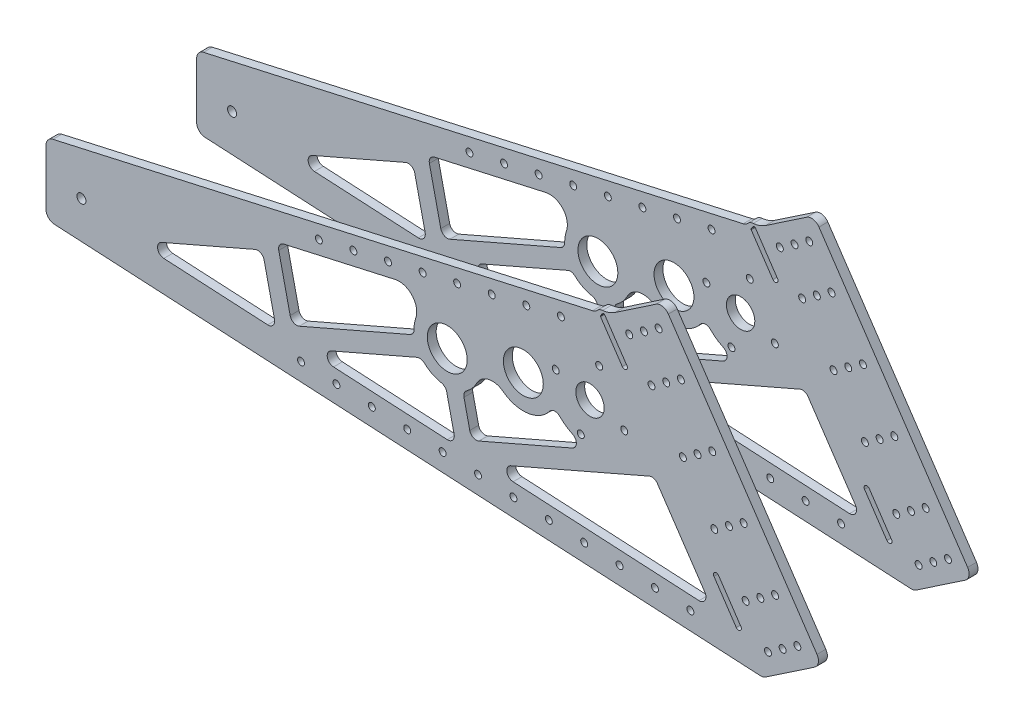
SolidWorks part; units mm, degrees
other "Markup1"
sketch "Sketch2"
sketch "Sketch9" plane through (0, 0, 0) normal (0, 0, 1) x (1, 0, 0)
sketch "Sketch12" plane through (116.0373, 167.646, 63.5) normal (0, 0, 1) x (1, 0, 0)
sketch "Sketch13" plane through (116.0373, 167.646, 63.5) normal (0, 0, 1) x (1, 0, 0)
sketch "Sketch14" plane through (116.0373, 167.646, 63.5) normal (0, 0, 1) x (1, 0, 0)
sketch "Sketch16" plane through (116.0373, 167.646, 63.5) normal (0, 0, 1) x (1, 0, 0)
sketch "Sketch17" plane through (116.0373, 167.8557, 63.5) normal (0, 0, 1) x (1, 0, 0)
sketch "Sketch18" plane through (116.0373, 167.7906, 57.15) normal (0, 0, 1) x (1, 0, 0)
sketch "Sketch19" plane through (84.5137, 127.089, 57.15) normal (0, 0, 1) x (1, 0, 0)
sketch "Sketch21" plane through (128.7373, 167.7931, 57.15) normal (0, 0, 1) x (1, 0, 0)
material "6061-T6 (SS)"
ref_plane "Front Plane" through (0, 0, 0) normal (0, 0, 1) x (1, 0, 0)
ref_plane "Top Plane" through (0, 0, 0) normal (0, 1, 0) x (1, 0, 0)
ref_plane "Right Plane" through (0, 0, 0) normal (1, 0, 0) x (0, 0, -1)
sketch "Grid" plane through (0, 0, 0) normal (0, 0, 1) x (1, 0, 0)
  line L0 (-23.2766, 0) -> (153.3593, 0) construction
  line L1 (0, 0) -> (0, 151.4205) construction
  line L6 (-1009.65, 1168.4) -> (-1009.65, 0) construction
  line L15 (-361.95, 520.7) -> (-803.275, 520.7)
  line L16 (-361.95, 520.7) -> (-361.95, 0)
  line L17 (-361.95, 0) -> (-803.275, 0)
  line L18 (-803.275, 520.7) -> (-803.275, 0)
  line L19 (-803.275, 0) -> (-1244.6, 0)
  line L20 (-803.275, 0) -> (-803.275, 825.5)
  line L21 (-803.275, 825.5) -> (-1244.6, 825.5)
  line L22 (-1244.6, 0) -> (-1244.6, 825.5)
  line L23 (-1030.732, 0) -> (-988.568, 0)
  line L24 (-1030.732, 0) -> (-1030.732, 1168.4)
  line L25 (-1030.732, 1168.4) -> (-988.568, 1168.4)
  line L26 (-988.568, 0) -> (-988.568, 1168.4)
  line L27 (-598.932, 0) -> (-556.768, 0)
  line L28 (-598.932, 0) -> (-598.932, 863.6)
  line L29 (-598.932, 863.6) -> (-556.768, 863.6)
  line L30 (-556.768, 0) -> (-556.768, 863.6)
  line L31 (-577.85, 863.6) -> (-577.85, 0) construction
  line L32 (-361.95, 520.7) -> (-361.95, 596.9) construction
  line L33 (-803.275, 825.5) -> (-803.275, 901.7) construction
  line L34 (-370.0766, 0) -> (-263.7141, 304.8)
  line L35 (-263.7141, 304.8) -> (-157.3516, 0)
  line L36 (-157.3516, 0) -> (-370.0766, 0)
  circle A0 centre (-100.3958, 159.9664) radius 120.65
  dimension "D3" = 241.3
  dimension "D2" = 76.2
  dimension "D4" = 304.8
  dimension "D5" = 212.725
  dimension "D7" = 42.164
  dimension "D8" = 520.7
  dimension "D9" = 304.8
  dimension "D10" = 1168.4
  dimension "D11" = 863.6
  dimension "D12" = 361.95
  dimension "D13" = 577.85
  dimension "D14" = 803.275
  dimension "D15" = 1009.65
sketch "ChassisXY" plane through (0, 0, 0) normal (0, 0, 1) x (1, 0, 0)
  line L0 (755.65, 93.726) -> (95.25, 93.726)
  line L1 (755.65, 93.726) -> (755.65, 42.926)
  line L2 (755.65, 42.926) -> (95.25, 42.926)
  line L3 (95.25, 93.726) -> (95.25, 42.926)
  line L15 (736.7108, 119.126) -> (675.4349, 119.126)
  line L16 (787.4, 42.926) -> (768.35, 42.926)
  line L19 (63.5, 169.926) -> (82.55, 169.926)
  line L20 (736.7108, 119.126) -> (694.5957, 90.719) construction
  line L21 (736.7108, 119.126) -> (717.55, 147.533) construction
  line L22 (694.5957, 90.719) -> (675.4349, 119.126) construction
  line L23 (717.55, 147.533) -> (675.4349, 119.126) construction
  line L27 (63.5, 169.926) -> (63.5, 42.926)
  line L31 (88.9, 42.926) -> (88.9, 1979.9925) construction
  line L32 (62.806, 1979.9925) -> (762, 1979.9925) construction
  line L33 (63.5, 42.926) -> (82.55, 42.926)
  line L36 (88.9, 1320.8) -> (762, 1320.8) construction
  line L37 (88.9, 988.6997) -> (131.0151, 1017.1067) construction
  line L45 (63.5, 42.926) -> (31.75, 42.926)
  line L46 (717.55, 147.533) -> (675.4349, 119.126) construction
  line L47 (717.55, 147.533) -> (-518.4596, 1979.9925) construction
  line L48 (675.4349, 119.126) -> (-560.5747, 1951.5855) construction
  line L49 (-518.4596, 1979.9925) -> (-560.5747, 1951.5855) construction
  line L50 (63.5, 42.926) -> (63.5, 169.926)
  line L51 (0, 74.676) -> (0, 138.176)
  line L52 (31.75, 169.926) -> (63.5, 169.926)
  line L54 (425.45, 93.726) -> (425.45, 42.926) construction
  line L55 (762, 42.926) -> (762, 1979.9925) construction
  line L56 (819.15, 169.926) -> (787.4, 169.926)
  line L57 (850.9, 74.676) -> (850.9, 138.176)
  line L58 (787.4, 42.926) -> (787.4, 169.926)
  line L59 (787.4, 42.926) -> (819.15, 42.926)
  line L60 (82.55, 169.926) -> (82.55, 42.926)
  line L61 (768.35, 169.926) -> (768.35, 42.926)
  line L62 (787.4, 169.926) -> (768.35, 169.926)
  line L63 (787.4, 169.926) -> (787.4, 42.926)
  line L64 (0, 0) -> (0, 200151.4205) construction
  line L65 (-200023.2766, 0) -> (200153.3593, 0) construction
  line L66 (95.25, 152.4) -> (755.65, 152.4) construction
  arc A5 (31.75, 169.926) -> (0, 138.176) centre (31.75, 138.176) ccw
  arc A6 (0, 74.676) -> (31.75, 42.926) centre (31.75, 74.676) ccw
  circle A7 centre (31.75, 74.676) radius 31.75 construction
  circle A8 centre (31.75, 138.176) radius 31.75 construction
  circle A9 centre (819.15, 138.176) radius 31.75 construction
  circle A10 centre (819.15, 74.676) radius 31.75 construction
  arc A11 (850.9, 74.676) -> (819.15, 42.926) centre (819.15, 74.676) cw
  arc A12 (819.15, 169.926) -> (850.9, 138.176) centre (819.15, 138.176) cw
  dimension "D3" = 63.5
  dimension "D1" = 50.8
  dimension "D2" = 56
  dimension "D4" = 38.1
  dimension "D5" = 50.8
  dimension "D6" = 12.7
  dimension "D7" = 19.05
  dimension "D8" = 42.926
  dimension "D9" = 109.474
  dimension "D10" = 25.4
  dimension "D12" = 660.4
  dimension "D13" = 6.35
ref_plane "Plane1" through (561.5696, 378.7835, 0) normal (0.829, 0.5592, 0) x (-0.5592, 0.829, 0)
sketch "carriage geo" plane through (0, 0, 0) normal (0, 0, 1) x (1, 0, 0)
  line L1 (116.0373, 195.326) -> (624.0373, 195.326)
  line L2 (116.0373, 195.326) -> (116.0373, 246.126)
  line L3 (116.0373, 246.126) -> (624.0373, 246.126)
  line L4 (624.0373, 195.326) -> (624.0373, 246.126)
  line L6 (624.0373, 195.326) -> (700.6322, 195.326) construction
  line L17 (717.55, 147.533) -> (-518.4596, 1979.9925) construction
  line L24 (624.0373, 246.126) -> (666.3671, 246.126) construction
  line L33 (666.3671, 246.126) -> (700.6322, 195.326) construction
  line L35 (675.4349, 119.126) -> (-560.5747, 1951.5855) construction
  line L64 (755.65, 93.726) -> (95.25, 93.726) construction
  circle A0 centre (154.1373, 220.726) radius 14.2875
  circle A58 centre (256.8816, 507.741) radius 25.4
  line B0 (120.4355, 364.2548) -> (144.4436, 355.656) construction
  line B1 (345.3934, 565.2279) -> (248.3868, 535.0242)
  line B2 (339.9907, 375.4447) -> (343.9447, 374.0285) construction
  line B3 (348.2442, 386.0326) -> (300.3235, 403.196) construction
  line B4 (308.577, 413.7839) -> (348.5895, 399.4529)
  line B5 (107.1432, 327.1426) -> (206.8255, 291.4401)
  line B6 (112.3162, 360.4178) -> (103.3062, 335.2619)
  line B7 (352.5436, 398.0367) -> (348.5895, 399.4529) construction
  line B8 (366.599, 439.1494) -> (341.413, 442.4393) construction
  line B9 (353.8882, 537.9448) -> (341.413, 442.4393) construction
  line B10 (343.9447, 374.0285) -> (352.5436, 398.0367)
  line B11 (348.5895, 399.4529) -> (308.577, 413.7839)
  line B12 (304.6229, 415.2001) -> (296.0241, 391.1919)
  line B13 (299.9781, 389.7757) -> (339.9907, 375.4447)
  line B14 (140.4752, 344.576) -> (141.8914, 348.5301) construction
  line B15 (129.3385, 325.9381) -> (133.2925, 324.5219) construction
  line B16 (110.7006, 337.0748) -> (109.2844, 333.1207) construction
  line B17 (121.8372, 355.7127) -> (117.8832, 357.1289) construction
  line B18 (117.8832, 357.1289) -> (110.7006, 337.0748)
  line B19 (109.2844, 333.1207) -> (129.3385, 325.9381)
  line B20 (141.8914, 348.5301) -> (121.8372, 355.7127)
  line B21 (133.2925, 324.5219) -> (140.4752, 344.576)
  line B22 (296.0241, 391.1919) -> (299.9781, 389.7757) construction
  line B23 (308.577, 413.7839) -> (304.6229, 415.2001) construction
  arc B24 (248.3868, 535.0242) -> (233.4586, 491.3735) centre (256.8816, 507.741) ccw
  circle B25 centre (256.8816, 507.741) radius 3.1877
  circle B26 centre (353.8882, 537.9448) radius 3.1877
  arc B27 (107.1432, 327.1426) -> (103.3062, 335.2619) centre (109.2844, 333.1207) cw
  circle B28 centre (341.413, 442.4393) radius 30 construction
  arc B29 (121.2422, 363.9009) -> (112.3162, 360.4178) centre (118.2943, 358.2767) ccw
  arc B30 (233.4586, 491.3735) -> (121.2422, 363.9009) centre (161.817, 441.3116) cw
  circle B31 centre (341.413, 442.4393) radius 25.4 construction
  circle B32 centre (366.599, 439.1494) radius 2.4892
  circle B33 centre (338.1231, 417.2533) radius 2.4892
  circle B34 centre (316.2269, 445.7292) radius 2.4892
  circle B35 centre (344.7029, 467.6254) radius 2.4892
  circle B36 centre (341.413, 442.4393) radius 10.16
  circle B37 centre (147.3899, 326.2177) radius 2.4892
  arc B38 (376.4624, 520.4251) -> (367.6342, 457.9958) centre (426.6271, 481.4924) ccw
  arc B39 (367.6342, 457.9958) -> (206.8255, 291.4401) centre (249.6484, 411.0026) cw
  arc B40 (133.2925, 324.5219) -> (129.3385, 325.9381) centre (131.3155, 325.23) cw
  arc B41 (343.9447, 374.0285) -> (339.9907, 375.4447) centre (341.9677, 374.7366) cw
  arc B42 (296.0241, 391.1919) -> (299.9781, 389.7757) centre (298.0011, 390.4838) ccw
  arc B43 (352.5436, 398.0367) -> (348.5895, 399.4529) centre (350.5666, 398.7448) ccw
  arc B44 (304.6229, 415.2001) -> (308.577, 413.7839) centre (306.5999, 414.492) cw
  arc B45 (109.2844, 333.1207) -> (110.7006, 337.0748) centre (109.9925, 335.0977) cw
  arc B46 (117.8832, 357.1289) -> (121.8372, 355.7127) centre (119.8602, 356.4208) cw
  arc B47 (141.8914, 348.5301) -> (140.4752, 344.576) centre (141.1833, 346.553) cw
  circle B48 centre (353.8882, 537.9448) radius 28.575
  line B49 (343.9447, 374.0285) -> (296.1197, 391.1577)
  line B50 (343.9447, 374.0285) -> (318.251, 302.291)
  line B51 (296.1197, 391.1577) -> (270.426, 319.4201)
  line B52 (318.251, 302.291) -> (270.426, 319.4201) construction
  line B53 (141.8571, 348.4344) -> (133.2925, 324.5219) construction
  line B54 (165.7696, 339.8698) -> (237.5071, 314.1761)
  line B55 (157.205, 315.9573) -> (228.9426, 290.2636)
  line B56 (237.5071, 314.1761) -> (228.9426, 290.2636) construction
  line B57 (161.4873, 327.9136) -> (233.2249, 302.2198) construction
  line B58 (165.7696, 339.8698) -> (157.205, 315.9573)
  line B59 (133.2925, 324.5219) -> (157.205, 315.9573) construction
  line B60 (141.8571, 348.4344) -> (165.7696, 339.8698) construction
  line B61 (308.4359, 312.5514) -> (331.9885, 378.3108) construction
  line B62 (320.0322, 382.5931) -> (294.3385, 310.8556) construction
  arc B63 (155.075, 274.6929) -> (165.7608, 168.0174) centre (154.1373, 220.726) ccw
  circle B64 centre (176.5553, 212.6967) radius 2.4892
  circle B65 centre (158.3928, 197.2968) radius 2.4892
  circle B66 centre (135.9748, 205.3261) radius 2.4892
  circle B67 centre (131.7194, 228.7553) radius 2.4892
  circle B68 centre (149.8819, 244.1552) radius 2.4892
  circle B69 centre (172.2999, 236.1259) radius 2.4892
  circle B70 centre (154.1373, 220.726) radius 23.8125 construction
  circle B71 centre (308.4359, 312.5514) radius 2.4892
  arc B72 (165.7608, 168.0174) -> (155.075, 274.6929) centre (154.1373, 220.726) ccw construction
  circle B73 centre (227.2467, 304.361) radius 2.4892
  circle B74 centre (284.5234, 321.116) radius 2.4892
  arc B75 (290.7123, 376.06) -> (193.2811, 330.0162) centre (218.9748, 401.7538) cw
  arc B76 (318.251, 302.291) -> (165.7608, 168.0174) centre (120.5341, 373.1059) cw
  circle B77 centre (312.7182, 324.5077) radius 2.4892
  circle B78 centre (288.8057, 333.0722) radius 2.4892
  circle B79 centre (317.0005, 336.4639) radius 2.4892
  circle B80 centre (293.088, 345.0285) radius 2.4892
  circle B81 centre (321.2828, 348.4202) radius 2.4892
  circle B82 centre (297.3703, 356.9847) radius 2.4892
  circle B83 centre (325.5651, 360.3764) radius 2.4892
  circle B84 centre (301.6526, 368.941) radius 2.4892
  circle B85 centre (329.8473, 372.3327) radius 2.4892
  circle B86 centre (305.9348, 380.8972) radius 2.4892
  arc B87 (162.2796, 314.1398) -> (155.075, 274.6929) centre (155.4279, 295.0098) cw
  circle B88 centre (215.2905, 308.6433) radius 2.4892
  circle B89 centre (203.3342, 312.9256) radius 2.4892
  circle B90 centre (191.378, 317.2079) radius 2.4892
  circle B91 centre (179.4217, 321.4901) radius 2.4892
  circle B92 centre (167.4655, 325.7724) radius 2.4892
  dimension "D2" = 28.575
  dimension "D3" = 25.4
  dimension "D4" = 38.1
  dimension "D8" = 101.6
  dimension "D5" = 50.8
  dimension "D1" = 50.8
  dimension "D6" = 12.7
  dimension "D7" = 508
sketch_block_instance "Block25-1"
sketch_block "Block25"
sketch_block_instance "Block26-1"
sketch_block "Block26"
sketch "carrriageyz" plane through (561.5696, 378.7835, 0) normal (0.829, 0.5592, 0) x (-0.5592, 0.829, 0)
  line L0 (-313.2035, 69.85) -> (769.957, 69.85) construction
  line L1 (769.957, -69.85) -> (-313.2035, -69.85) construction
  line L2 (-262.4035, 69.85) -> (-262.4035, -69.85) construction
  line L4 (-313.2035, 69.85) -> (-313.2035, -69.85) construction
  line L5 (-313.2035, 0) -> (-278.9385, 0) construction
  line L6 (769.957, 69.85) -> (769.957, -69.85) construction
  line L7 (-249.7114, 57.15) -> (-249.7114, 50.8)
  line L8 (-249.7114, 57.15) -> (-97.3114, 57.15)
  line L9 (-249.7114, 50.8) -> (-97.3114, 50.8)
  line L10 (-97.3114, 57.15) -> (-97.3114, 50.8)
  line L11 (106.8647, 0) -> (-106.8647, 0) construction
  line L12 (-97.3114, -57.15) -> (-97.3114, -50.8)
  line L13 (-249.7114, -50.8) -> (-97.3114, -50.8)
  line L14 (-249.7114, -57.15) -> (-97.3114, -57.15)
  line L15 (-249.7114, -57.15) -> (-249.7114, -50.8)
  line L16 (-218.5469, 31.75) -> (-148.6639, 31.75)
  line L17 (-174.4547, 57.15) -> (-206.8488, 57.15)
  line L19 (-221.2897, -57.15) -> (-160.0138, -57.15)
  line L21 (-219.5489, -57.15) -> (-127.4739, -57.15)
  line L22 (-219.5489, 63.5) -> (-127.4739, 63.5)
  line L23 (-219.5489, 63.5) -> (-219.5489, 57.15)
  line L24 (-219.5489, 57.15) -> (-127.4739, 57.15)
  line L25 (-127.4739, 63.5) -> (-127.4739, 57.15)
  line L26 (-127.4739, -63.5) -> (-127.4739, -57.15)
  line L27 (-219.5489, -63.5) -> (-127.4739, -63.5)
  line L28 (-219.5489, -63.5) -> (-219.5489, -57.15)
  line L29 (-218.5469, 31.75) -> (-218.5469, -31.75)
  line L30 (-218.5469, -31.75) -> (-148.6639, -31.75)
  line L31 (-148.6639, 31.75) -> (-148.6639, -31.75)
  line L33 (-97.3114, -69.1134) -> (-125.8864, -69.1134)
  line L34 (-97.3114, 57.15) -> (-125.8864, 57.15)
  line L35 (-97.3114, 57.15) -> (-97.3114, 69.1134)
  line L36 (-97.3114, 69.1134) -> (-125.8864, 69.1134)
  line L37 (-125.8864, 57.15) -> (-125.8864, 69.1134)
  line L38 (-249.7114, 57.15) -> (-221.1364, 57.15)
  line L39 (-249.7114, 57.15) -> (-249.7114, 69.1134)
  line L40 (-249.7114, 69.1134) -> (-221.1364, 69.1134)
  line L41 (-221.1364, 57.15) -> (-221.1364, 69.1134)
  line L42 (-125.8864, -57.15) -> (-125.8864, -69.1134)
  line L43 (-97.3114, -57.15) -> (-125.8864, -57.15)
  line L44 (-97.3114, -57.15) -> (-97.3114, -69.1134)
  line L45 (-249.7114, -69.1134) -> (-221.1364, -69.1134)
  line L46 (-221.1364, -57.15) -> (-221.1364, -69.1134)
  line L47 (-249.7114, -57.15) -> (-221.1364, -57.15)
  line L48 (-249.7114, -57.15) -> (-249.7114, -69.1134)
  line L49 (-111.5989, 69.1134) -> (-111.5989, -69.1134) construction
  line L50 (-235.4239, 69.1134) -> (-235.4239, -69.1134) construction
  point P4 (-313.2035, 0)
  point P31 (-148.6639, 0)
  point P41 (-190.6518, 57.15)
  point P53 (-111.5989, 0)
  dimension "D1" = 139.7
  dimension "D2" = 12.7
  dimension "D3" = 6.35
  dimension "D4" = 63.5
  dimension "D5" = 6.35
  dimension "D6" = 152.4
  dimension "D7" = 28.575
  dimension "D8" = 11.9634
  dimension "D9" = 50.8
  dimension "D10" = 1.5875
  dimension "D11" = 1.5875
ref_plane "bearing block interface plane" through (0, 0, 57.15) normal (0, 0, 1) x (1, 0, 0)
sketch "bearing block interface plate" plane through (0, 0, 57.15) normal (0, 0, 1) x (1, 0, 0)
  line L0 (529.0514, 336.1484) -> (571.1665, 364.5554)
  line L1 (529.0514, 336.1484) -> (642.6794, 167.688)
  line L2 (571.1665, 364.5554) -> (684.7945, 196.095)
  line L3 (642.6794, 167.688) -> (684.7945, 196.095)
  line L4 (675.4349, 119.126) -> (-560.5747, 1951.5855) construction
  line L5 (717.55, 147.533) -> (-518.4596, 1979.9925) construction
  line L6 (635.5777, 178.2167) -> (677.6928, 206.6237) construction
  line L7 (585.8654, 251.9182) -> (627.9805, 280.3252) construction
  line L10 (545.0304, 312.4586) -> (587.1455, 340.8656) construction
  line L12 (528.3092, 320.3288) -> (546.682, 332.7214) construction
  line L15 (606.2073, 289.894) -> (628.6962, 256.5529) construction
  line L16 (522.4272, 322.7212) -> (526.7202, 333.2764) construction
  line L17 (529.0514, 336.1484) -> (536.1532, 325.6196) construction
  line L18 (527.0768, 314.0996) -> (540.247, 311.4938) construction
  line L21 (577.876, 263.7631) -> (619.9911, 292.1701) construction
  line L22 (626.7005, 191.3777) -> (668.8156, 219.7847) construction
  line L23 (611.7695, 190.2657) -> (623.1643, 190.2921) construction
  line L24 (610.7216, 215.0675) -> (652.8367, 243.4745) construction
  line L25 (605.5175, 197.8065) -> (608.0351, 210.9939) construction
  line L26 (611.7548, 196.6157) -> (630.1275, 209.0082) construction
  circle A0 centre (646.1065, 185.3185) radius 2.4892
  circle A1 centre (656.6352, 192.4202) radius 2.4892
  circle A2 centre (667.164, 199.522) radius 2.4892
  circle A3 centre (567.7395, 346.9249) radius 2.4892
  circle A4 centre (557.2107, 339.8231) radius 2.4892
  circle A5 centre (546.682, 332.7214) radius 2.4892
  arc A7 (522.4272, 322.7212) -> (527.0768, 314.0996) centre (528.3092, 320.3288) ccw construction
  circle A12 centre (562.6609, 309.0316) radius 2.4892
  circle A13 centre (573.1897, 316.1334) radius 2.4892
  circle A14 centre (583.7185, 323.2351) radius 2.4892
  circle A15 centre (606.2073, 289.894) radius 2.4892
  circle A16 centre (595.6786, 282.7922) radius 2.4892
  circle A17 centre (585.1498, 275.6905) radius 2.4892
  circle A18 centre (628.6962, 256.5529) radius 2.4892
  circle A19 centre (618.1674, 249.4511) radius 2.4892
  circle A20 centre (607.6387, 242.3494) radius 2.4892
  circle A21 centre (651.1851, 223.2117) radius 2.4892
  circle A22 centre (640.6563, 216.11) radius 2.4892
  circle A23 centre (630.1275, 209.0082) radius 2.4892
  arc A24 (526.7202, 333.2764) -> (529.0514, 336.1484) centre (532.6023, 330.884) cw construction
  arc A25 (540.247, 311.4938) -> (545.0304, 312.4586) centre (541.4795, 317.723) ccw construction
  arc A29 (623.1643, 190.2921) -> (626.7005, 191.3777) centre (623.1496, 196.6421) ccw construction
  arc A30 (611.7695, 190.2657) -> (605.5175, 197.8065) centre (611.7548, 196.6157) cw construction
  arc A31 (608.0351, 210.9939) -> (610.7216, 215.0675) centre (614.2724, 209.8031) cw construction
  point P28 (617.4518, 273.2234)
  point P72 (0, 0)
  dimension "D3" = 4.9784
  dimension "D8" = 12.7
  dimension "D10" = 2
  dimension "D13" = 6.35
  dimension "D1" = 12.7
  dimension "D2" = 12.7
  dimension "D4" = 12.7
  dimension "D5" = 28.575
  dimension "D6" = 203.2
  dimension "D7" = 33.3375
  dimension "D9" = 9.4615
  dimension "D11" = 4
  dimension "D12" = 12.7
extrude "Boss-Extrude1" add sketch "bearing block interface plate" against normal blind 6.35
fillet "Fillet2" radius 6.35 4 edges at (642.6794, 167.688, 53.975) (571.1665, 364.5554, 53.975) (529.0514, 336.1484, 53.975) (684.7945, 196.095, 53.975)
ref_plane "carriage support plane" through (0, 0, 57.15) normal (0, 0, 1) x (1, 0, 0)
sketch "plate+gb" plane through (0, 0, 57.15) normal (0, 0, 1) x (1, 0, 0)
  line L1 (717.55, 147.533) -> (-518.4596, 1979.9925) construction
  line L3 (116.0373, 195.326) -> (624.0373, 195.326) construction
  line L4 (128.7373, 195.326) -> (642.6794, 167.688)
  line L8 (532.6023, 330.884) -> (639.1286, 172.9523) construction
  line L10 (116.0373, 246.126) -> (624.0373, 246.126) construction
  line L11 (128.7373, 246.126) -> (128.7373, 195.326)
  line L12 (116.0373, 195.326) -> (116.0373, 246.126) construction
  line L13 (571.1665, 364.5554) -> (529.0514, 336.1484)
  line L17 (527.3934, 335.03) -> (543.3723, 311.3403) construction
  line L18 (529.0514, 336.1484) -> (545.0304, 312.4586)
  line L19 (416.2866, 258.7212) -> (154.1373, 220.726) construction
  line L20 (416.2683, 274.9957) -> (154.0767, 274.701) construction
  line L21 (420.8895, 243.1112) -> (169.4032, 168.9548) construction
  line L22 (518.57, 277.876) -> (525.144, 302.4105) construction
  line L24 (527.3966, 335.7763) -> (128.7373, 246.126)
  line L26 (256.3165, 274.8159) -> (527.3966, 335.7763) construction
  line L27 (528.1615, 331.9493) -> (527.3934, 335.03) construction
  line L30 (525.7353, 333.9116) -> (541.7142, 310.2219)
  line L31 (529.0514, 336.1484) -> (642.6794, 167.688) construction
  line L38 (642.6794, 167.688) -> (684.7945, 196.095) construction
  line L39 (642.6794, 167.688) -> (684.7945, 196.095)
  line L40 (545.0304, 312.4586) -> (587.1455, 340.8656) construction
  line L43 (609.0635, 213.9491) -> (625.0424, 190.2593) construction
  line L44 (610.7216, 215.0675) -> (626.7005, 191.3777)
  line L45 (607.4054, 212.8307) -> (623.3843, 189.1409)
  line L59 (684.7945, 196.095) -> (571.1665, 364.5554)
  circle A0 centre (470.8051, 270.9813) radius 14.2875
  circle A1 centre (416.2866, 258.7212) radius 14.2875
  arc A2 (155.075, 274.6929) -> (165.7608, 168.0174) centre (154.1373, 220.726) ccw construction
  arc A4 (165.7608, 168.0174) -> (155.075, 274.6929) centre (154.1373, 220.726) ccw construction
  circle A5 centre (518.57, 277.876) radius 10.16
  circle A12 centre (518.57, 277.876) radius 25.4 construction
  circle A13 centre (518.57, 277.876) radius 7.62 construction
  circle A14 centre (470.8051, 270.9813) radius 40.64 construction
  circle A15 centre (470.8051, 270.9813) radius 15.24 construction
  circle A16 centre (416.2866, 258.7212) radius 40.64 construction
  circle A17 centre (416.2866, 258.7212) radius 16.2745 construction
  circle A18 centre (525.144, 302.4105) radius 2.4892
  circle A19 centre (543.1045, 271.302) radius 2.4892
  circle A20 centre (511.996, 253.3415) radius 2.4892
  circle A21 centre (494.0355, 284.45) radius 2.4892
  arc A22 (529.0514, 336.1484) -> (525.7353, 333.9116) centre (527.3934, 335.03) ccw
  arc A23 (541.7142, 310.2219) -> (545.0304, 312.4586) centre (543.3723, 311.3403) ccw
  arc A24 (610.7216, 215.0675) -> (607.4054, 212.8307) centre (609.0635, 213.9491) ccw
  circle A25 centre (607.6387, 242.3494) radius 2.4892 construction
  circle A26 centre (618.1674, 249.4511) radius 2.4892 construction
  circle A27 centre (628.6962, 256.5529) radius 2.4892 construction
  circle A28 centre (606.2073, 289.894) radius 2.4892 construction
  circle A29 centre (595.6786, 282.7922) radius 2.4892 construction
  circle A30 centre (585.1498, 275.6905) radius 2.4892 construction
  circle A31 centre (562.6609, 309.0316) radius 2.4892 construction
  circle A32 centre (573.1897, 316.1334) radius 2.4892 construction
  circle A33 centre (583.7185, 323.2351) radius 2.4892 construction
  circle A35 centre (518.57, 277.876) radius 30 construction
  circle A41 centre (607.6387, 242.3494) radius 2.4892
  circle A42 centre (618.1674, 249.4511) radius 2.4892
  circle A43 centre (628.6962, 256.5529) radius 2.4892
  circle A44 centre (606.2073, 289.894) radius 2.4892
  circle A45 centre (595.6786, 282.7922) radius 2.4892
  circle A46 centre (585.1498, 275.6905) radius 2.4892
  circle A47 centre (562.6609, 309.0316) radius 2.4892
  circle A48 centre (573.1897, 316.1334) radius 2.4892
  circle A49 centre (583.7185, 323.2351) radius 2.4892
  arc A59 (623.3843, 189.1409) -> (626.7005, 191.3777) centre (625.0424, 190.2593) ccw
  circle A63 centre (567.7395, 346.9249) radius 2.4892 construction
  circle A68 centre (557.2107, 339.8231) radius 2.4892 construction
  circle A74 centre (546.682, 332.7214) radius 2.4892 construction
  circle A75 centre (651.1851, 223.2117) radius 2.4892 construction
  circle A77 centre (640.6563, 216.11) radius 2.4892 construction
  circle A78 centre (630.1275, 209.0082) radius 2.4892 construction
  circle A79 centre (567.7395, 346.9249) radius 2.4892
  circle A80 centre (557.2107, 339.8231) radius 2.4892
  circle A81 centre (546.682, 332.7214) radius 2.4892
  circle A82 centre (651.1851, 223.2117) radius 2.4892
  circle A83 centre (640.6563, 216.11) radius 2.4892
  circle A84 centre (630.1275, 209.0082) radius 2.4892
  circle A85 centre (646.1065, 185.3185) radius 2.4892 construction
  circle A86 centre (656.6352, 192.4202) radius 2.4892 construction
  circle A87 centre (667.164, 199.522) radius 2.4892 construction
  arc A88 (530.9003, 337.3954) -> (522.7356, 334.7281) centre (528.1615, 331.9493) ccw
  arc A89 (527.61, 338.0203) -> (536.5393, 341.1991) centre (525.8867, 356.9922) ccw
  arc A90 (528.6076, 336.8064) -> (525.985, 333.5754) centre (532.6023, 330.884) ccw
  circle A91 centre (646.1065, 185.3185) radius 2.4892
  circle A93 centre (656.6352, 192.4202) radius 2.4892
  circle A94 centre (667.164, 199.522) radius 2.4892
  arc A95 (530.3158, 337.652) -> (525.9764, 333.5542) centre (532.6023, 330.884) ccw
  point P10 (535.3828, 323.1851)
  point P47 (617.053, 202.1042)
  point P64 (518.57, 277.876)
  dimension "D2" = 50.8
  dimension "D15" = 28.575
  dimension "D16" = 20.32
  dimension "D18" = 4.9784
  dimension "D14" = 6.096
  dimension "D24" = 19.05
  dimension "D19" = 15
  dimension "D20" = 31.75
  dimension "D11" = 4
  dimension "D8" = 41.275
  dimension "D9" = 50.8
  dimension "D10" = 50.8
  dimension "D12" = 12.7
  dimension "D21" = 20
  dimension "D23" = 3.175
  dimension "D13" = 0.7937
  dimension "D17" = 4
extrude "Boss-Extrude2" add sketch "plate+gb" against normal blind 6.35 contours L13 L11 L4 A49 A48 A47 A46 A45 A44 A43 A42 A41 A94 A93 A91 A21 A20 A19 A18 A5 A1 | L24 A22 L18 L13 | A95 L24 A22 L30 | A95 A22 L24 | L13 A95 A22 | A88 L13 region at (431.8972, 241.8927, 57.15) region at (526.1373, 336.7007, 57.15) region at (526.8519, 336.2597, 57.15) region at (526.1352, 334.8528, 57.15) region at (531.5413, 338.4981, 57.15) region at (529.6272, 336.9641, 57.15)
fillet "Fillet1" radius 6.35 6 edges at (128.7373, 195.326, 53.975) (128.7373, 246.126, 53.975) (571.1665, 364.5554, 53.975) (642.6794, 167.688, 53.975) (684.7945, 196.095, 53.975) (522.7356, 334.7281, 53.975)
sketch "tube" plane through (0, 0, 57.15) normal (0, 0, 1) x (1, 0, 0)
  line L7 (522.5096, 324.9144) -> (135.7839, 237.9478)
  line L11 (135.4283, 207.6845) -> (641.235, 180.484)
  line L12 (135.4283, 207.6845) -> (641.235, 180.484) construction
  line L13 (522.5096, 324.9144) -> (135.7839, 237.9478) construction
  circle A41 centre (154.1373, 220.726) radius 3.2639
  circle A48 centre (497.7285, 319.3416) radius 2.4892
  circle A49 centre (472.9474, 313.7689) radius 2.4892
  circle A50 centre (448.1662, 308.1961) radius 2.4892
  circle A51 centre (423.3851, 302.6233) radius 2.4892
  circle A52 centre (398.604, 297.0506) radius 2.4892
  circle A53 centre (373.8229, 291.4778) radius 2.4892
  circle A54 centre (590.5083, 183.2119) radius 2.4892
  circle A55 centre (565.1449, 184.5758) radius 2.4892
  circle A56 centre (539.7816, 185.9398) radius 2.4892
  circle A57 centre (514.4182, 187.3038) radius 2.4892
  circle A58 centre (489.0549, 188.6677) radius 2.4892
  circle A59 centre (463.6915, 190.0317) radius 2.4892
  circle A60 centre (438.3282, 191.3956) radius 2.4892
  circle A61 centre (412.9648, 192.7596) radius 2.4892
  circle A62 centre (387.6015, 194.1235) radius 2.4892
  circle A63 centre (362.2381, 195.4875) radius 2.4892
  circle A64 centre (336.8748, 196.8514) radius 2.4892
  circle A65 centre (311.5114, 198.2154) radius 2.4892
  circle A70 centre (349.0417, 285.905) radius 2.4892
  circle A71 centre (324.2606, 280.3323) radius 2.4892
  dimension "D3" = 12.7
  dimension "D14" = 6.5278
  dimension "D4" = 4.9784
  dimension "D5" = 50.8
  dimension "D15" = 25.4
  dimension "D7" = 12
  dimension "D11" = 9.525
  dimension "D16" = 25.4
  dimension "D6" = 25.4
extrude "Cut-Extrude1" cut sketch "tube" against normal up to next
sketch "Sketch20" plane through (0, 0, 57.15) normal (0, 0, 1) x (1, 0, 0)
  line L0 (178.8573, 214.8878) -> (288.2885, 262.48) construction
  line L1 (288.2885, 262.48) -> (300.4616, 208.3484) construction
  line L2 (300.4616, 208.3484) -> (416.2866, 258.7212) construction
  line L3 (416.2866, 258.7212) -> (429.1709, 201.4268) construction
  line L4 (429.1709, 201.4268) -> (561.0825, 258.7959) construction
  line L5 (181.3898, 209.0647) -> (283.7782, 253.5939)
  line L6 (283.7782, 253.5939) -> (295.9513, 199.4623)
  line L7 (295.9513, 199.4623) -> (411.7763, 249.8352)
  line L8 (173.8491, 236.745) -> (522.9963, 315.261)
  line L9 (522.9963, 315.261) -> (606.1998, 191.9068)
  line L10 (606.1998, 191.9068) -> (178.8573, 214.8878)
  line L11 (134.7464, 195.0029) -> (640.553, 167.8023) construction
  line L12 (520.4198, 334.2073) -> (133.6942, 247.2407) construction
  line L13 (525.9764, 333.5542) -> (541.7142, 310.2219) construction
  line L14 (128.7373, 241.0454) -> (128.7373, 201.3437) construction
  line L15 (411.7763, 249.8352) -> (424.6606, 192.5407)
  line L16 (424.6606, 192.5407) -> (564.6938, 253.4419)
  line L17 (176.3248, 220.711) -> (292.7988, 271.3661)
  line L18 (292.7988, 271.3661) -> (304.9719, 217.2345)
  line L19 (304.9719, 217.2345) -> (420.7969, 267.6073)
  line L20 (420.7969, 267.6073) -> (433.6812, 210.3129)
  line L21 (433.6812, 210.3129) -> (558.55, 264.619)
  line L22 (424.6606, 192.5407) -> (563.6151, 252.9727) construction
  arc A0 (378.9306, 282.8636) -> (393.7412, 266.3854) centre (381.717, 270.473) cw
  arc A1 (492.8846, 262.0635) -> (548.723, 277.1196) centre (518.57, 277.876) ccw
  circle A2 centre (518.57, 277.876) radius 10.16 construction
  circle A3 centre (511.996, 253.3415) radius 4.7625 construction
  circle A8 centre (154.1373, 220.726) radius 25.4
  circle A9 centre (416.2866, 258.7212) radius 23.8125
  circle A10 centre (470.8051, 270.9813) radius 23.8125
  circle A12 centre (416.2866, 258.7212) radius 14.2875 construction
  arc A13 (430.701, 277.6754) -> (449.6639, 281.9398) centre (438.3887, 287.7843) ccw
  arc A14 (437.4277, 247.7628) -> (456.3907, 252.0272) centre (448.703, 241.9183) cw
  dimension "D4" = 9.525
  dimension "D5" = 12.7
  dimension "D6" = 9.525
  dimension "D1" = 22.225
  dimension "D2" = 19.05
  dimension "D3" = 12.7
  dimension "D7" = 6.35
  dimension "D8" = 6.35
extrude "Cut-Extrude2" cut sketch "Sketch20" against normal up to next contours L10 L6 L5 | A9 A0 L8 L18 L19 | A9 L7 L10 L15 | A14 A9 L20 L21 A1 A10 | L16 L10 L9 region at (256.8929, 225.4741, 57.15) region at (381.5439, 218.4291, 57.15) region at (342.1598, 254.4584, 57.15) region at (538.0781, 215.3378, 57.15) region at (463.244, 237.3713, 57.15)
fillet "Fillet3" radius 4.7625 17 edges at (392.7081, 255.3914, 53.975) (304.9719, 217.2345, 53.975) (294.4838, 263.8732, 53.975) (492.8846, 262.0635, 53.975) (519.7296, 247.7358, 53.975) (433.6812, 210.3129, 53.975) (427.5171, 237.7234, 53.975) (564.6938, 253.4419, 53.975) (606.1998, 191.9068, 53.975) (443.3407, 200.6648, 53.975) (415.1266, 234.937, 53.975) (422.5827, 201.7811, 53.975) (314.6314, 207.5864, 53.975) (397.7731, 243.7451, 53.975) (283.7782, 253.5939, 53.975) (293.8733, 208.7027, 53.975) (193.0271, 214.1258, 53.975)
fillet "Fillet4" radius 0.635 2 edges at (528.4731, 336.7135, 53.975) (525.9764, 333.5542, 53.975)
mirror "Mirror1" about plane through (0, 0, 0) normal (0, 0, 1) of bodies 115 105 104 101
equation "\"D3@plate+gb\" = 12 / 20"
equation "\"D4@plate+gb\" = 64 / 20"
equation "\"D5@plate+gb\" = 24 / 20"
equation "\"D6@plate+gb\" = 64 / 20"
equation "\"D7@plate+gb\" = 0.25 /  ( sin ( 180 / 16 )  ) "
equation "\"D22@plate+gb\"=60mm"
